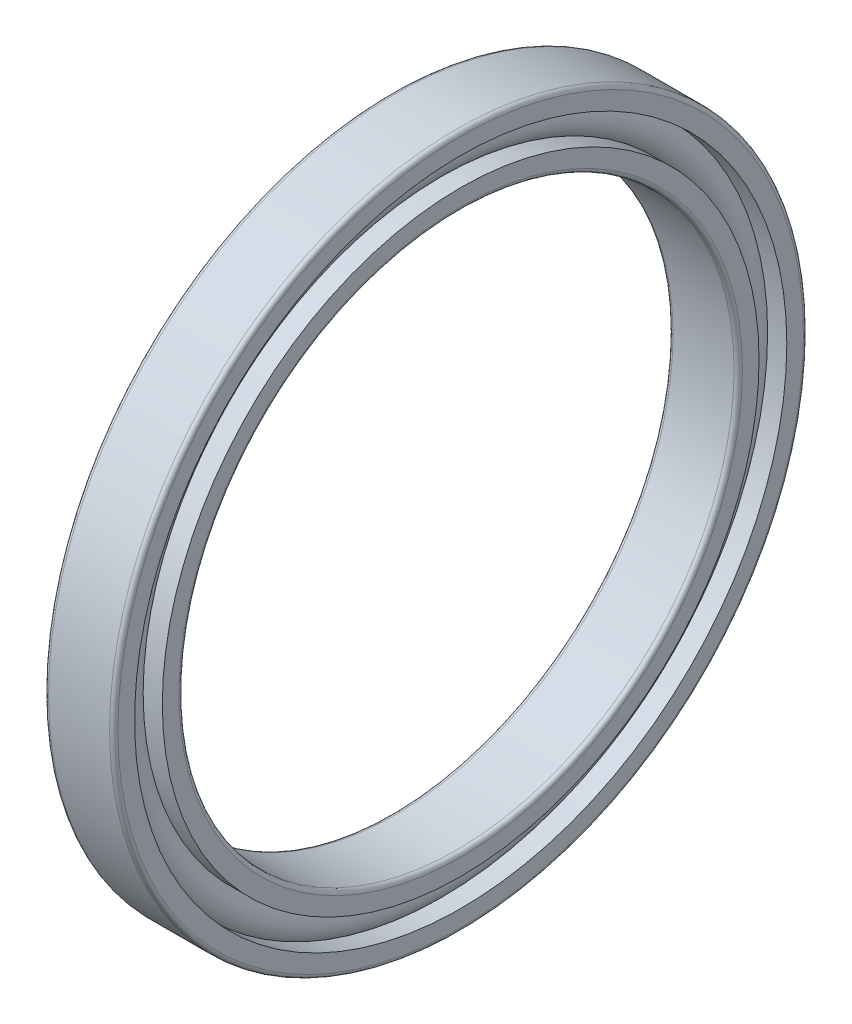
SolidWorks part; units mm, degrees
ref_plane "Plane1" through (0, 0, 0) normal (0, 0, 1) x (1, 0, 0)
ref_plane "Plane2" through (0, 0, 0) normal (0, 1, 0) x (1, 0, 0)
ref_plane "Plane3" through (0, 0, 0) normal (1, 0, 0) x (0, 0, -1)
other "Configuration Table"
sketch "Clipboard" plane through (0, 0, 0) normal (0, 0, 1) x (1, 0, 0)
  line L0 (-10, 0) -> (10, 0) construction
  line L1 (0, 0) -> (22.3471, -0.7804)
  line L2 (0, 0) -> (44.9726, 1.5705)
  line L3 (0, 0) -> (22.3471, -0.7804)
  line L4 (0, 0) -> (-22.3573, -0.3902)
  dimension "BallCLRad" = 45
sketch "CagSpiSke" plane through (0, 0, 0) normal (0, 0, 1) x (1, 0, 0)
  line L0 (0.3, 44.5) -> (0.3, 45.5)
  line L1 (0.3, 45.5) -> (-0.3, 45.5)
  line L2 (-0.3, 45.5) -> (-0.3, 44.5)
  line L3 (-0.3, 44.5) -> (0.3, 44.5)
  line L4 (-20.6375, 0) -> (20.6375, 0) construction
  line L5 (0, 0) -> (0, 23.7692) construction
  dimension "OD" = 91
  dimension "ID" = 89
revolve "CageSpine" add sketch "CagSpiSke" angle 0.001 about L4 reverse direction yes
ref_axis "Axis1" through (-50, 0, 0) along (1, 0, 0)
sketch "CagBalSke" plane through (0, 0, 0) normal (0, 0, 1) x (1, 0, 0)
  line L0 (-3.3, 45) -> (3.3, 45)
  line L1 (-1.905, 45) -> (1.905, 45) construction
  line L2 (-10, 0) -> (10, 0) construction
  line L3 (0, 0) -> (0, 24) construction
  arc A0 (3.3, 45) -> (-3.3, 45) centre (0, 45) cw
  dimension "BallCLRad" = 45
revolve "CageBall" [suppressed] add sketch "CagBalSke" angle 360 about L1 reverse direction yes
pattern_circular "CageBalls" [suppressed] count 2 every 180 about axis through (-50, 0, 0) along (1, 0, 0)
sketch "CagTrmODSke" plane through (0, 0, 0) normal (0, 0, 1) x (1, 0, 0)
  line L0 (3.301, 45.5) -> (3.301, 48.301)
  line L1 (3.301, 48.301) -> (-3.301, 48.301)
  line L2 (-3.301, 48.301) -> (-3.301, 45.5)
  line L3 (-3.301, 45.5) -> (3.301, 45.5)
  line L4 (-20.6375, 0) -> (20.6375, 0) construction
  line L5 (0, 0) -> (0, 25) construction
  dimension "Width" = 6.602
  dimension "ID" = 91
  dimension "OD" = 96.602
revolve "CageTrimOD" [suppressed] cut sketch "CagTrmODSke" angle 360 about L4 reverse direction yes
sketch "CagTrmIDSke" plane through (0, 0, 0) normal (0, 0, 1) x (1, 0, 0)
  line L0 (3.301, 41.701) -> (3.301, 44.5)
  line L1 (3.301, 44.5) -> (-3.301, 44.5)
  line L2 (-3.301, 44.5) -> (-3.301, 41.701)
  line L3 (-3.301, 41.701) -> (3.301, 41.701)
  line L4 (-20.6375, 0) -> (20.6375, 0) construction
  line L5 (0, 0) -> (0, 25) construction
  dimension "Width" = 6.602
  dimension "ID" = 83.402
  dimension "OD" = 89
revolve "CageTrimID" [suppressed] cut sketch "CagTrmIDSke" angle 360 about L4 reverse direction yes
sketch "BalSimSke" plane through (0, 0, 0) normal (0, 0, 1) x (1, 0, 0)
  line L0 (-10, 0) -> (10, 0) construction
  line L1 (-10, 45) -> (10, 45) construction
  line L2 (0, 0) -> (0, 23) construction
  circle A0 centre (0, 45) radius 3
  dimension "BallCLRad" = 45
  dimension "Ball_diameter" = 6
revolve "BallsSimplified" add sketch "BalSimSke" angle 360 about L0
sketch "BalDetSke" plane through (0, 0, 0) normal (0, 0, 1) x (1, 0, 0)
  line L0 (-3, 45) -> (3, 45)
  line L1 (-1.905, 45) -> (1.905, 45) construction
  line L2 (0, 0) -> (0, 25) construction
  arc A0 (3, 45) -> (-3, 45) centre (0, 45) cw
  dimension "BallCLRad" = 45
  dimension "Ball_diameter" = 6
revolve "BallDetailed" [suppressed] add sketch "BalDetSke" angle 360 about L1 reverse direction yes
sketch "InnRacSke" plane through (0, 0, 0) normal (0, 0, 1) x (1, 0, 0)
  line L0 (-2.2024, 43) -> (-5, 43)
  line L1 (-5, 43) -> (-5, 40.6)
  line L2 (-4.4, 40) -> (4.4, 40)
  line L3 (5, 40.6) -> (5, 43)
  line L4 (5, 43) -> (2.2024, 43)
  line L5 (-20.6375, 0) -> (20.6375, 0) construction
  line L6 (0, 0) -> (0, 30) construction
  arc A0 (-5, 40.6) -> (-4.4, 40) centre (-4.4, 40.6) ccw
  arc A1 (4.4, 40) -> (5, 40.6) centre (4.4, 40.6) ccw
  arc A2 (2.2024, 43) -> (-2.2024, 43) centre (0, 45) cw
  dimension "BallCLRad" = 45
  dimension "Fillet_radius" = 0.6
  dimension "Ball_diameter" = 5.95
  dimension "ID" = 80
  dimension "OD" = 86
  dimension "Width" = 10
revolve "InnerRace" add sketch "InnRacSke" angle 360 about L5 reverse direction yes
sketch "OutRacSke" plane through (0, 0, 0) normal (0, 0, 1) x (1, 0, 0)
  line L0 (-2.2024, 47) -> (-5, 47)
  line L1 (-5, 47) -> (-5, 49.4)
  line L2 (-4.4, 50) -> (4.4, 50)
  line L3 (5, 49.4) -> (5, 47)
  line L4 (5, 47) -> (2.2024, 47)
  line L5 (-20.6375, 0) -> (20.6375, 0) construction
  line L6 (0, 0) -> (0, 30) construction
  arc A0 (-5, 49.4) -> (-4.4, 50) centre (-4.4, 49.4) cw
  arc A1 (4.4, 50) -> (5, 49.4) centre (4.4, 49.4) cw
  arc A2 (2.2024, 47) -> (-2.2024, 47) centre (0, 45) ccw
  dimension "BallCLRad" = 45
  dimension "Fillet_radius" = 0.6
  dimension "Ball_diameter" = 5.95
  dimension "Width" = 10
revolve "OuterRace" add sketch "OutRacSke" angle 360 about L5 reverse direction yes
pattern_circular "BallsDetailed" [suppressed] count 2 every 180 about axis through (-50, 0, 0) along (1, 0, 0)
equation "\"BallCLRad@Clipboard\" = ( \"OD@OutRacSke\" + \"ID@InnRacSke\" ) / 4"
equation "\"BallCLRad@BalSimSke\" = \"BallCLRad@Clipboard\""
equation "\"BallCLRad@BalDetSke\" = \"BallCLRad@Clipboard\""
equation "\"BallCLRad@InnRacSke\" = \"BallCLRad@Clipboard\""
equation "\"BallCLRad@OutRacSke\" = \"BallCLRad@Clipboard\""
equation "\"Ball_diameter@InnRacSke\" = \"Ball_diameter@BalDetSke\" - 0.05"
equation "\"Ball_diameter@OutRacSke\" = \"Ball_diameter@BalDetSke\" - 0.05"
equation "\"Ball_diameter@BalSimSke\" = \"Ball_diameter@BalDetSke\""
equation "\"Width@OutRacSke\" = \"Width@InnRacSke\""
equation "\"Fillet_radius@OutRacSke\" = \"Fillet_radius@InnRacSke\""
equation "\"Max_count@Clipboard\" = int( 3.14159265 / atn(( \"Ball_diameter@BalDetSke\" / 2) / sqr( \"BallCLRad@Clipboard\"  *  \"BallCLRad@Clipboard\" - ( \"Ball_diameter@BalDetSke\" / 2) *  ( \"Ball_diameter@BalDetSke\" / 2))))"
equation "\"Max_count@Clipboard\" = ((sgn( \"Max_count@Clipboard\" - \"Count@Clipboard\" )-1)*( \"Max_count@Clipboard\" - \"Count@Clipboard\" ))/-2+ \"Count@Clipboard\""
equation "\"Count@BallsDetailed\" = int( \"Show_count@Clipboard\" ) "
equation "\"Count@BallsDetailed\" = ((sgn( \"Count@BallsDetailed\" - \"Max_count@Clipboard\" )-1)*( \"Count@BallsDetailed\" - \"Max_count@Clipboard\" ))/-2+ \"Max_count@Clipboard\""
equation "\"Count@BallsDetailed\" = ((sgn( \"Count@BallsDetailed\" - \"Min_count@Clipboard\" )+1)*( \"Count@BallsDetailed\" - \"Min_count@Clipboard\"))/2 +\"Min_count@Clipboard\""
equation "\"Angle@BallsDetailed\" = 360.0 / \"Max_count@Clipboard\""
equation "\"BallCLRad@CagBalSke\" = \"BallCLRad@Clipboard\""
equation "\"Count@CageBalls\" = \"Count@BallsDetailed\""
equation "\"Angle@CageBalls\" = \"Angle@BallsDetailed\""
equation "\"Angle@CageSpine\" =  \"Angle@CageBalls\" * ( \"Count@CageBalls\" -1 + int( \"Count@CageBalls\" / \"Max_count@Clipboard\" ) )  + 0.001 -  int( \"Count@CageBalls\" / \"Max_count@Clipboard\" ) * 0.001"
equation "\"Angle@CageSpine\" =  \"Angle@CageSpine\" * int( \"Min_count@Clipboard\" / 2) + int(1 / \"Min_count@Clipboard\")  * 0.001"
equation "\"CageWallOD@CagBalSke\" =  \"Ball_diameter@BalDetSke\" * 1.1"
equation "\"Thickness@CagSpiSke\" =  \"Ball_diameter@BalDetSke\" * 0.1"
equation "\"OD@CagTrmODSke\" = \"BallCLRad@Clipboard\" * 2 + \"CageWallOD@CagBalSke\" + 0.002"
equation "\"ID@CagTrmODSke\" = \"BallCLRad@Clipboard\" * 2 + \"Ball_diameter@BalDetSke\" / 6"
equation "\"OD@CagTrmIDSke\" = \"BallCLRad@Clipboard\" * 2 - \"Ball_diameter@BalDetSke\" / 6"
equation "\"ID@CagTrmIDSke\" = \"BallCLRad@Clipboard\" * 2 - \"CageWallOD@CagBalSke\" + 0.002"
equation "\"OD@CagSpiSke\" = \"ID@CagTrmODSke\""
equation "\"ID@CagSpiSke\" = \"OD@CagTrmIDSke\""
equation "\"Width@CagTrmODSke\" = \"CageWallOD@CagBalSke\" + 0.002"
equation "\"Width@CagTrmIDSke\" = \"CageWallOD@CagBalSke\" + 0.002"
